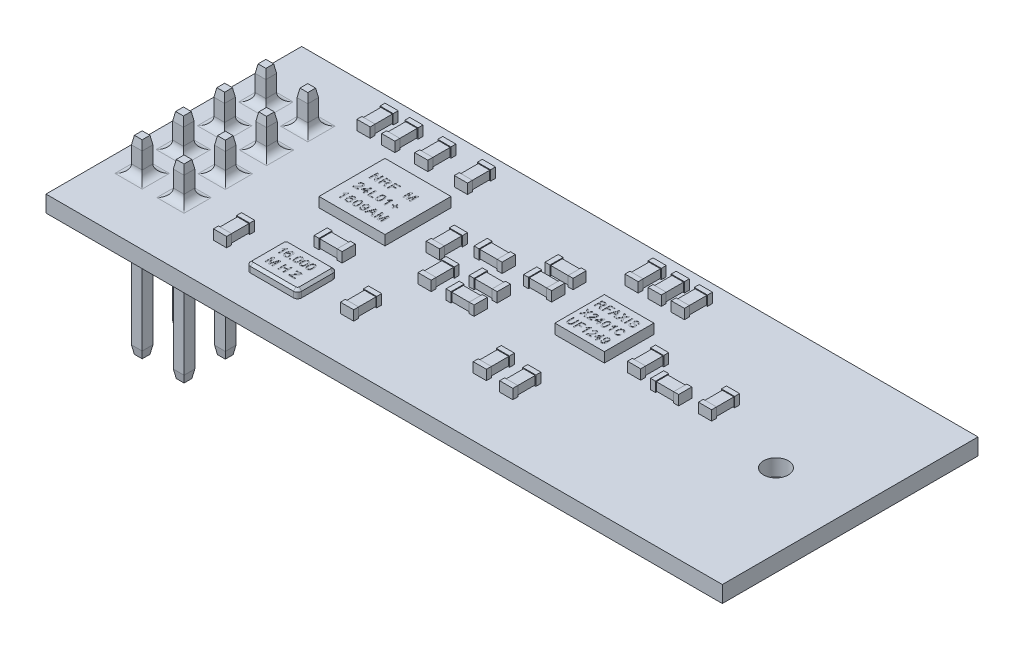
SolidWorks part; units mm, degrees
ref_plane "Спереди" through (0, 0, 0) normal (0, 0, 1) x (1, 0, 0)
ref_plane "Сверху" through (0, 0, 0) normal (0, 1, 0) x (1, 0, 0)
ref_plane "Справа" through (0, 0, 0) normal (1, 0, 0) x (0, 0, -1)
sketch "Эскиз1" plane through (0, 0, 0) normal (0, 1, 0) x (1, 0, 0)
  line L1 (0, -7.75) -> (41, -7.75)
  line L2 (0, -7.75) -> (0, 7.75)
  line L3 (0, 7.75) -> (41, 7.75)
  line L4 (41, -7.75) -> (41, 7.75)
  dimension "D1" = 41
  dimension "D2" = 15.5
extrude "Бобышка-Вытянуть1" add sketch "Эскиз1" along normal blind 1
sketch "Эскиз2" plane through (0, 0, 0) normal (0, -1, 0) x (1, 0, 0)
  line L0 (0, 0) -> (0.6, 0) construction
  line L1 (0, -7.75) -> (0, 7.75) construction
  line L2 (0.6, 4.5) -> (0.6, 3)
  line L3 (0.6, 3) -> (1.1, 2.5)
  line L4 (1.1, 2.5) -> (0.6, 2)
  line L5 (0.6, 2) -> (0.6, 0.5)
  line L6 (0.6, 0.5) -> (1.1, 0)
  line L7 (1.1, 0) -> (0.6, -0.5)
  line L8 (0.6, -0.5) -> (0.6, -2)
  line L9 (0.6, -2) -> (1.1, -2.5)
  line L10 (1.1, -2.5) -> (0.6, -3)
  line L11 (0.6, -3) -> (0.6, -4.5)
  line L12 (0.6, -4.5) -> (1.1, -5)
  line L13 (1.1, -5) -> (5.1, -5)
  line L14 (5.1, -5) -> (5.6, -4.5)
  line L15 (5.6, -4.5) -> (5.6, -3)
  line L16 (5.6, -3) -> (5.1, -2.5)
  line L17 (5.1, -2.5) -> (5.6, -2)
  line L18 (5.6, -2) -> (5.6, -0.5)
  line L19 (5.6, -0.5) -> (5.1, 0)
  line L20 (5.1, 0) -> (5.6, 0.5)
  line L21 (5.6, 0.5) -> (5.6, 2)
  line L22 (5.6, 2) -> (5.1, 2.5)
  line L23 (5.1, 2.5) -> (5.6, 3)
  line L24 (5.6, 3) -> (5.6, 4.5)
  line L25 (5.6, 4.5) -> (5.1, 5)
  line L26 (5.1, 5) -> (1.1, 5)
  line L27 (1.1, 5) -> (0.6, 4.5)
  line L28 (0.6, 0.5) -> (0.6, -0.5) construction
  line L29 (1.1, 2.5) -> (5.1, 2.5) construction
  line L30 (1.1, 0) -> (5.1, 0) construction
  line L31 (1.1, -2.5) -> (5.1, -2.5) construction
  dimension "D1" = 5
  dimension "D2" = 10
  dimension "D3" = 0.5
  dimension "D4" = 0.6
extrude "Бобышка-Вытянуть2" add sketch "Эскиз2" along normal blind 2.5
sketch "Эскиз3" plane through (0, -2.5, 0) normal (0, -1, 0) x (1, 0, 0)
  line L0 (3.1, 5) -> (3.1, -5) construction
  line L1 (5.1, 5) -> (1.1, 5) construction
  line L2 (1.1, -5) -> (5.1, -5) construction
  line L3 (1.83, 3.75) -> (4.37, 3.75) construction
  line L4 (0.6, 3.75) -> (1.83, 3.75) construction
  line L5 (0.6, 4.5) -> (0.6, 3) construction
  line L6 (0.6, 1.25) -> (1.83, 1.25) construction
  line L7 (0.6, 2) -> (0.6, 0.5) construction
  line L8 (1.83, 1.25) -> (4.37, 1.25) construction
  line L9 (4.37, 1.25) -> (4.37, 3.75) construction
  line L10 (1.83, 3.75) -> (1.83, 1.25) construction
  line L11 (0.6, -1.25) -> (1.83, -1.25) construction
  line L12 (0.6, -0.5) -> (0.6, -2) construction
  line L13 (1.83, -1.25) -> (1.83, 1.25) construction
  line L14 (1.83, -1.25) -> (4.37, -1.25) construction
  line L15 (4.37, -1.25) -> (4.37, 1.25) construction
  line L16 (0.6, -3.75) -> (1.83, -3.75) construction
  line L17 (0.6, -3) -> (0.6, -4.5) construction
  line L18 (1.83, -3.75) -> (1.83, -1.25) construction
  line L19 (1.83, -3.75) -> (4.37, -3.75) construction
  line L20 (4.37, -3.75) -> (4.37, -1.25) construction
  line L21 (1.505, 4.075) -> (2.155, 3.425) construction
  line L22 (1.505, 3.425) -> (2.155, 3.425)
  line L23 (1.505, 3.425) -> (1.505, 4.075)
  line L24 (1.505, 4.075) -> (2.155, 4.075)
  line L25 (2.155, 3.425) -> (2.155, 4.075)
  line L26 (4.045, 3.425) -> (4.695, 3.425)
  line L27 (4.045, 3.425) -> (4.045, 4.075)
  line L28 (4.045, 4.075) -> (4.695, 4.075)
  line L29 (4.695, 3.425) -> (4.695, 4.075)
  line L30 (1.505, 0.925) -> (2.155, 0.925)
  line L31 (1.505, 0.925) -> (1.505, 1.575)
  line L32 (1.505, 1.575) -> (2.155, 1.575)
  line L33 (2.155, 0.925) -> (2.155, 1.575)
  line L34 (4.045, 0.925) -> (4.695, 0.925)
  line L35 (4.045, 0.925) -> (4.045, 1.575)
  line L36 (4.045, 1.575) -> (4.695, 1.575)
  line L37 (4.695, 0.925) -> (4.695, 1.575)
  line L38 (1.505, -1.575) -> (2.155, -1.575)
  line L39 (1.505, -1.575) -> (1.505, -0.925)
  line L40 (1.505, -0.925) -> (2.155, -0.925)
  line L41 (2.155, -1.575) -> (2.155, -0.925)
  line L42 (4.045, -1.575) -> (4.695, -1.575)
  line L43 (4.045, -1.575) -> (4.045, -0.925)
  line L44 (4.045, -0.925) -> (4.695, -0.925)
  line L45 (4.695, -1.575) -> (4.695, -0.925)
  line L46 (1.505, -4.075) -> (2.155, -4.075)
  line L47 (1.505, -4.075) -> (1.505, -3.425)
  line L48 (1.505, -3.425) -> (2.155, -3.425)
  line L49 (2.155, -4.075) -> (2.155, -3.425)
  line L50 (4.045, -4.075) -> (4.695, -4.075)
  line L51 (4.045, -4.075) -> (4.045, -3.425)
  line L52 (4.045, -3.425) -> (4.695, -3.425)
  line L53 (4.695, -4.075) -> (4.695, -3.425)
  line L54 (4.045, 4.075) -> (4.695, 3.425) construction
  line L55 (1.505, 1.575) -> (2.155, 0.925) construction
  line L56 (4.045, 1.575) -> (4.695, 0.925) construction
  line L57 (1.505, -0.925) -> (2.155, -1.575) construction
  line L58 (4.045, -0.925) -> (4.695, -1.575) construction
  line L59 (1.505, -3.425) -> (2.155, -4.075) construction
  line L60 (4.045, -3.425) -> (4.695, -4.075) construction
  point P8 (3.1, 3.75)
  dimension "D1" = 2.54
  dimension "D2" = 0.65
extrude "Бобышка-Вытянуть3" add sketch "Эскиз3" along normal blind 6
sketch "Эскиз8" plane through (0, 1, 0) normal (0, 1, 0) x (1, 0, 0)
  line L0 (2.155, -3.425) -> (2.155, -4.075) construction
  line L1 (1.505, 3.425) -> (2.155, 3.425)
  line L2 (1.505, 3.425) -> (1.505, 4.075)
  line L3 (1.505, 4.075) -> (2.155, 4.075)
  line L4 (2.155, 3.425) -> (2.155, 4.075)
  line L5 (4.045, 3.425) -> (4.695, 3.425)
  line L6 (4.045, 3.425) -> (4.045, 4.075)
  line L7 (4.045, 4.075) -> (4.695, 4.075)
  line L8 (4.695, 3.425) -> (4.695, 4.075)
  line L9 (1.505, 0.925) -> (2.155, 0.925)
  line L10 (1.505, 0.925) -> (1.505, 1.575)
  line L11 (1.505, 1.575) -> (2.155, 1.575)
  line L12 (2.155, 0.925) -> (2.155, 1.575)
  line L13 (4.045, 0.925) -> (4.695, 0.925)
  line L14 (4.045, 0.925) -> (4.045, 1.575)
  line L15 (4.045, 1.575) -> (4.695, 1.575)
  line L16 (4.695, 0.925) -> (4.695, 1.575)
  line L17 (1.505, -1.575) -> (2.155, -1.575)
  line L18 (1.505, -1.575) -> (1.505, -0.925)
  line L19 (1.505, -0.925) -> (2.155, -0.925)
  line L20 (2.155, -1.575) -> (2.155, -0.925)
  line L21 (4.045, -1.575) -> (4.695, -1.575)
  line L22 (4.045, -1.575) -> (4.045, -0.925)
  line L23 (4.045, -0.925) -> (4.695, -0.925)
  line L24 (4.695, -1.575) -> (4.695, -0.925)
  line L25 (1.505, -4.075) -> (2.155, -4.075)
  line L26 (1.505, -4.075) -> (1.505, -3.425)
  line L27 (1.505, -3.425) -> (2.155, -3.425)
  line L28 (2.155, -4.075) -> (2.155, -3.425)
  line L30 (4.045, -4.075) -> (4.695, -4.075)
  line L31 (4.045, -4.075) -> (4.045, -3.425)
  line L32 (4.045, -3.425) -> (4.695, -3.425)
  line L33 (4.695, -4.075) -> (4.695, -3.425)
extrude "Бобышка-Вытянуть5" add sketch "Эскиз8" along normal blind 2
chamfer "Фаска1" distance 0.5 angle 10 64 edges at (4.37, -8.5, -4.075) (4.695, -8.5, -3.75) (4.37, -8.5, -3.425) (4.045, -8.5, -3.75) (2.155, -8.5, -3.75) (1.83, -8.5, -4.075) (1.505, -8.5, -3.75) (1.83, -8.5, -3.425) (4.37, -8.5, -1.575) (4.695, -8.5, -1.25) (4.37, -8.5, -0.925) (4.045, -8.5, -1.25) (2.155, -8.5, -1.25) (1.83, -8.5, -1.575) (1.505, -8.5, -1.25) (1.83, -8.5, -0.925) (4.37, -8.5, 0.925) (4.695, -8.5, 1.25) (4.37, -8.5, 1.575) (4.045, -8.5, 1.25) (2.155, -8.5, 1.25) (1.83, -8.5, 0.925) (1.505, -8.5, 1.25) (1.83, -8.5, 1.575) (4.37, -8.5, 3.425) (4.695, -8.5, 3.75) (4.37, -8.5, 4.075) (4.045, -8.5, 3.75) (2.155, -8.5, 3.75) (1.83, -8.5, 4.075) (1.505, -8.5, 3.75) (1.83, -8.5, 3.425) (4.695, 3, -3.75) (4.37, 3, -4.075) (4.045, 3, -3.75) (4.37, 3, -3.425) (2.155, 3, -3.75) (1.83, 3, -4.075) (1.505, 3, -3.75) (1.83, 3, -3.425) (4.695, 3, -1.25) (4.37, 3, -1.575) (4.045, 3, -1.25) (4.37, 3, -0.925) (2.155, 3, -1.25) (1.83, 3, -1.575) (1.505, 3, -1.25) (1.83, 3, -0.925) (4.695, 3, 1.25) (4.37, 3, 0.925) (4.045, 3, 1.25) (4.37, 3, 1.575) (2.155, 3, 1.25) (1.83, 3, 0.925) (1.505, 3, 1.25) (1.83, 3, 1.575) (4.695, 3, 3.75) (4.37, 3, 3.425) (4.045, 3, 3.75) (4.37, 3, 4.075) (2.155, 3, 3.75) (1.83, 3, 3.425) (1.505, 3, 3.75) (1.83, 3, 4.075)
fillet "Скругление1" radius 0.5 32 edges at (1.83, 1, 3.425) (1.505, 1, 3.75) (2.155, 1, 3.75) (1.83, 1, 4.075) (4.695, 1, -3.75) (4.37, 1, -4.075) (4.045, 1, -3.75) (4.37, 1, -3.425) (2.155, 1, -3.75) (1.83, 1, -4.075) (1.505, 1, -3.75) (1.83, 1, -3.425) (4.695, 1, -1.25) (4.37, 1, -1.575) (4.045, 1, -1.25) (4.37, 1, -0.925) (2.155, 1, -1.25) (1.83, 1, -1.575) (1.505, 1, -1.25) (1.83, 1, -0.925) (2.155, 1, 1.25) (1.83, 1, 0.925) (1.505, 1, 1.25) (1.83, 1, 1.575) (4.695, 1, 1.25) (4.37, 1, 0.925) (4.045, 1, 1.25) (4.37, 1, 1.575) (4.695, 1, 3.75) (4.37, 1, 3.425) (4.045, 1, 3.75) (4.37, 1, 4.075)
sketch "Эскиз5" plane through (0, 1, 0) normal (0, 1, 0) x (1, 0, 0)
  line L0 (305.5, -0.012) -> (1527.5, -0.012) construction
  line L1 (41, 0) -> (39.5, 0) construction
  line L2 (33.5, -3) -> (39.5, -3) construction
  line L3 (33.5, -3) -> (33.5, 3) construction
  line L4 (33.5, 3) -> (39.5, 3) construction
  line L5 (39.5, -3) -> (39.5, 3) construction
  line L6 (41, -7.75) -> (41, 7.75) construction
  line L7 (33.5, 3) -> (39.5, -3) construction
  circle A0 centre (36.5, 0) radius 0.75
  dimension "D4" = 1.5
  dimension "D1" = 6
  dimension "D2" = 1.5
  dimension "D3" = 6
sketch "Эскиз9" plane through (0, 1, 0) normal (0, 1, 0) x (1, 0, 0)
  line L0 (6.5, 6.4) -> (6.5, 5.3) construction
  line L1 (6.1, 6.4) -> (6.9, 6.4)
  line L2 (6.1, 6.4) -> (6.1, 6.7)
  line L3 (6.1, 6.7) -> (6.9, 6.7)
  line L4 (6.9, 6.4) -> (6.9, 6.7)
  line L5 (7.6, 6.4) -> (8.4, 6.4)
  line L6 (7.6, 6.4) -> (7.6, 6.7)
  line L7 (7.6, 6.7) -> (8.4, 6.7)
  line L8 (8.4, 6.4) -> (8.4, 6.7)
  line L9 (9.6, 6.4) -> (10.4, 6.4)
  line L10 (9.6, 6.4) -> (9.6, 6.7)
  line L11 (9.6, 6.7) -> (10.4, 6.7)
  line L12 (10.4, 6.4) -> (10.4, 6.7)
  line L13 (12, 6.4) -> (12.8, 6.4)
  line L14 (12, 6.4) -> (12, 6.7)
  line L15 (12, 6.7) -> (12.8, 6.7)
  line L16 (12.8, 6.4) -> (12.8, 6.7)
  line L17 (8, 6.4) -> (8, 5.3) construction
  line L18 (10, 6.4) -> (10, 5.3) construction
  line L19 (12.4, 6.4) -> (12.4, 5.3) construction
  line L20 (7.9, -3.7) -> (7.9, -4.8) construction
  line L21 (6.1, 5) -> (6.9, 5)
  line L22 (6.1, 5) -> (6.1, 5.3)
  line L23 (6.1, 5.3) -> (6.9, 5.3)
  line L24 (6.9, 5) -> (6.9, 5.3)
  line L25 (7.6, 5) -> (8.4, 5)
  line L26 (7.6, 5) -> (7.6, 5.3)
  line L27 (7.6, 5.3) -> (8.4, 5.3)
  line L28 (8.4, 5) -> (8.4, 5.3)
  line L29 (9.6, 5) -> (10.4, 5)
  line L30 (9.6, 5) -> (9.6, 5.3)
  line L31 (9.6, 5.3) -> (10.4, 5.3)
  line L32 (10.4, 5) -> (10.4, 5.3)
  line L33 (12, 5) -> (12.8, 5)
  line L34 (12, 5) -> (12, 5.3)
  line L35 (12, 5.3) -> (12.8, 5.3)
  line L36 (12.8, 5) -> (12.8, 5.3)
  line L37 (7.5, -3.7) -> (8.3, -3.7)
  line L38 (7.5, -3.7) -> (7.5, -3.4)
  line L39 (7.5, -3.4) -> (8.3, -3.4)
  line L40 (8.3, -3.7) -> (8.3, -3.4)
  line L41 (7.5, -5.1) -> (8.3, -5.1)
  line L42 (7.5, -5.1) -> (7.5, -4.8)
  line L43 (7.5, -4.8) -> (8.3, -4.8)
  line L44 (8.3, -5.1) -> (8.3, -4.8)
  line L45 (22.75, 6.4) -> (22.75, 5.3) construction
  line L46 (22.35, 6.7) -> (23.15, 6.7)
  line L47 (22.35, 6.7) -> (22.35, 6.4)
  line L48 (22.35, 6.4) -> (23.15, 6.4)
  line L49 (23.15, 6.7) -> (23.15, 6.4)
  line L50 (23.75, 6.7) -> (24.55, 6.7)
  line L51 (23.75, 6.7) -> (23.75, 6.4)
  line L52 (23.75, 6.4) -> (24.55, 6.4)
  line L53 (24.55, 6.7) -> (24.55, 6.4)
  line L54 (25.15, 6.7) -> (25.95, 6.7)
  line L55 (25.15, 6.7) -> (25.15, 6.4)
  line L56 (25.15, 6.4) -> (25.95, 6.4)
  line L57 (25.95, 6.7) -> (25.95, 6.4)
  line L58 (22.35, 5) -> (23.15, 5)
  line L59 (22.35, 5) -> (22.35, 5.3)
  line L60 (22.35, 5.3) -> (23.15, 5.3)
  line L61 (23.15, 5) -> (23.15, 5.3)
  line L62 (23.75, 5) -> (24.55, 5)
  line L63 (23.75, 5) -> (23.75, 5.3)
  line L64 (23.75, 5.3) -> (24.55, 5.3)
  line L65 (24.55, 5) -> (24.55, 5.3)
  line L66 (25.15, 5) -> (25.95, 5)
  line L67 (25.15, 5) -> (25.15, 5.3)
  line L68 (25.15, 5.3) -> (25.95, 5.3)
  line L69 (25.95, 5) -> (25.95, 5.3)
  line L70 (24.15, 6.4) -> (24.15, 5.3) construction
  line L71 (25.55, 6.4) -> (25.55, 5.3) construction
  line L72 (11.2, -2) -> (12.3, -2) construction
  line L73 (10.9, -2.4) -> (11.2, -2.4)
  line L74 (10.9, -2.4) -> (10.9, -1.6)
  line L75 (10.9, -1.6) -> (11.2, -1.6)
  line L76 (11.2, -2.4) -> (11.2, -1.6)
  line L77 (12.3, -2.4) -> (12.6, -2.4)
  line L78 (12.3, -2.4) -> (12.3, -1.6)
  line L79 (12.3, -1.6) -> (12.6, -1.6)
  line L80 (12.6, -2.4) -> (12.6, -1.6)
  line L81 (15.6, -3.7) -> (15.6, -4.8) construction
  line L82 (15.2, -3.4) -> (16, -3.4)
  line L83 (15.2, -3.4) -> (15.2, -3.7)
  line L84 (15.2, -3.7) -> (16, -3.7)
  line L85 (16, -3.4) -> (16, -3.7)
  line L86 (15.2, -5.1) -> (16, -5.1)
  line L87 (15.2, -5.1) -> (15.2, -4.8)
  line L88 (15.2, -4.8) -> (16, -4.8)
  line L89 (16, -5.1) -> (16, -4.8)
  line L90 (27.4, 1.9) -> (27.4, 0.8) construction
  line L91 (27, 1.9) -> (27.8, 1.9)
  line L92 (27, 1.9) -> (27, 2.2)
  line L93 (27, 2.2) -> (27.8, 2.2)
  line L94 (27.8, 1.9) -> (27.8, 2.2)
  line L95 (27, 0.5) -> (27.8, 0.5)
  line L96 (27, 0.5) -> (27, 0.8)
  line L97 (27, 0.8) -> (27.8, 0.8)
  line L98 (27.8, 0.5) -> (27.8, 0.8)
  line L99 (31.7, 1.9) -> (31.7, 0.8) construction
  line L100 (31.3, 2.2) -> (32.1, 2.2)
  line L101 (31.3, 2.2) -> (31.3, 1.9)
  line L102 (31.3, 1.9) -> (32.1, 1.9)
  line L103 (32.1, 2.2) -> (32.1, 1.9)
  line L104 (31.3, 0.5) -> (32.1, 0.5)
  line L105 (31.3, 0.5) -> (31.3, 0.8)
  line L106 (31.3, 0.8) -> (32.1, 0.8)
  line L107 (32.1, 0.5) -> (32.1, 0.8)
  line L108 (28.9, 0.7) -> (30, 0.7) construction
  line L109 (28.6, 0.3) -> (28.9, 0.3)
  line L110 (28.6, 0.3) -> (28.6, 1.1)
  line L111 (28.6, 1.1) -> (28.9, 1.1)
  line L112 (28.9, 0.3) -> (28.9, 1.1)
  line L113 (30, 0.3) -> (30.3, 0.3)
  line L114 (30, 0.3) -> (30, 1.1)
  line L115 (30, 1.1) -> (30.3, 1.1)
  line L116 (30.3, 0.3) -> (30.3, 1.1)
  line L117 (22.75, -2.8) -> (22.75, -3.9) construction
  line L118 (22.35, -2.8) -> (23.15, -2.8)
  line L119 (22.35, -2.8) -> (22.35, -2.5)
  line L120 (22.35, -2.5) -> (23.15, -2.5)
  line L121 (23.15, -2.8) -> (23.15, -2.5)
  line L122 (22.35, -4.2) -> (23.15, -4.2)
  line L123 (22.35, -4.2) -> (22.35, -3.9)
  line L124 (22.35, -3.9) -> (23.15, -3.9)
  line L125 (23.15, -4.2) -> (23.15, -3.9)
  line L126 (24.55, -3) -> (24.55, -4.1) construction
  line L127 (24.15, -3) -> (24.95, -3)
  line L128 (24.15, -3) -> (24.15, -2.7)
  line L129 (24.15, -2.7) -> (24.95, -2.7)
  line L130 (24.95, -3) -> (24.95, -2.7)
  line L131 (24.15, -4.4) -> (24.95, -4.4)
  line L132 (24.15, -4.4) -> (24.15, -4.1)
  line L133 (24.15, -4.1) -> (24.95, -4.1)
  line L134 (24.95, -4.4) -> (24.95, -4.1)
  line L135 (16.4, 0.2) -> (16.4, -0.9) construction
  line L136 (16, -1.2) -> (16.8, -1.2)
  line L137 (16, -1.2) -> (16, -0.9)
  line L138 (16, -0.9) -> (16.8, -0.9)
  line L139 (16.8, -1.2) -> (16.8, -0.9)
  line L140 (16, 0.2) -> (16.8, 0.2)
  line L141 (16, 0.2) -> (16, 0.5)
  line L142 (16, 0.5) -> (16.8, 0.5)
  line L143 (16.8, 0.2) -> (16.8, 0.5)
  line L144 (15, 2.1) -> (15, 1) construction
  line L145 (14.6, 0.7) -> (15.4, 0.7)
  line L146 (14.6, 0.7) -> (14.6, 1)
  line L147 (14.6, 1) -> (15.4, 1)
  line L148 (15.4, 0.7) -> (15.4, 1)
  line L149 (14.6, 2.1) -> (15.4, 2.1)
  line L150 (14.6, 2.1) -> (14.6, 2.4)
  line L151 (14.6, 2.4) -> (15.4, 2.4)
  line L152 (15.4, 2.1) -> (15.4, 2.4)
  line L153 (16.6, 2.3) -> (17.7, 2.3) construction
  line L154 (16.3, 1.9) -> (16.6, 1.9)
  line L155 (16.3, 1.9) -> (16.3, 2.7)
  line L156 (16.3, 2.7) -> (16.6, 2.7)
  line L157 (16.6, 1.9) -> (16.6, 2.7)
  line L158 (17.7, 1.9) -> (18, 1.9)
  line L159 (17.7, 1.9) -> (17.7, 2.7)
  line L160 (17.7, 2.7) -> (18, 2.7)
  line L161 (18, 1.9) -> (18, 2.7)
  line L162 (19.3, 1.9) -> (19.6, 1.9)
  line L163 (19.3, 1.9) -> (19.3, 2.7)
  line L164 (19.3, 2.7) -> (19.6, 2.7)
  line L165 (19.6, 1.9) -> (19.6, 2.7)
  line L166 (20.7, 1.9) -> (21, 1.9)
  line L167 (20.7, 1.9) -> (20.7, 2.7)
  line L168 (20.7, 2.7) -> (21, 2.7)
  line L169 (21, 1.9) -> (21, 2.7)
  line L170 (19.3, 3.2) -> (19.6, 3.2)
  line L171 (19.3, 3.2) -> (19.3, 4)
  line L172 (19.3, 4) -> (19.6, 4)
  line L173 (19.6, 3.2) -> (19.6, 4)
  line L174 (20.7, 3.2) -> (21, 3.2)
  line L175 (20.7, 3.2) -> (20.7, 4)
  line L176 (20.7, 4) -> (21, 4)
  line L177 (21, 3.2) -> (21, 4)
  line L178 (19.6, 2.3) -> (20.7, 2.3) construction
  line L179 (19.6, 3.6) -> (20.7, 3.6) construction
  line L180 (18, 0.6) -> (19.1, 0.6) construction
  line L181 (17.7, -1.2) -> (18, -1.2)
  line L182 (17.7, -1.2) -> (17.7, -0.4)
  line L183 (17.7, -0.4) -> (18, -0.4)
  line L184 (18, -1.2) -> (18, -0.4)
  line L185 (19.1, -1.2) -> (19.4, -1.2)
  line L186 (19.1, -1.2) -> (19.1, -0.4)
  line L187 (19.1, -0.4) -> (19.4, -0.4)
  line L188 (19.4, -1.2) -> (19.4, -0.4)
  line L189 (17.7, 0.2) -> (18, 0.2)
  line L190 (17.7, 0.2) -> (17.7, 1)
  line L191 (17.7, 1) -> (18, 1)
  line L192 (18, 0.2) -> (18, 1)
  line L193 (19.1, 0.2) -> (19.4, 0.2)
  line L194 (19.1, 0.2) -> (19.1, 1)
  line L195 (19.1, 1) -> (19.4, 1)
  line L196 (19.4, 0.2) -> (19.4, 1)
  line L197 (18, -0.8) -> (19.1, -0.8) construction
  dimension "D1" = 1.7
  dimension "D2" = 0.8
  dimension "D3" = 6.5
  dimension "D4" = 5
  dimension "D5" = 0.3
  dimension "D6" = 1.5
  dimension "D7" = 2
  dimension "D8" = 2.4
  dimension "D9" = 0.8
  dimension "D10" = 1.7
  dimension "D11" = 0.3
  dimension "D12" = 3.4
  dimension "D13" = 7.9
  dimension "D14" = 10.35
  dimension "D15" = 1.4
  dimension "D16" = 1.4
  dimension "D17" = 1.7
  dimension "D18" = 0.8
  dimension "D19" = 0.3
  dimension "D20" = 2
  dimension "D21" = 10.9
  dimension "D22" = 7.7
  dimension "D23" = 1.7
  dimension "D24" = 0.8
  dimension "D25" = 0.3
  dimension "D26" = 27.4
  dimension "D27" = 0.5
  dimension "D28" = 4.3
  dimension "D29" = 1.7
  dimension "D30" = 1.2
  dimension "D31" = 0.3
  dimension "D32" = 1.5
  dimension "D33" = 1.7
  dimension "D34" = 0.8
  dimension "D35" = 0.3
  dimension "D36" = 7.15
  dimension "D37" = 2.5
  dimension "D38" = 1.8
  dimension "D39" = 0.2
  dimension "D40" = 0.8
  dimension "D41" = 1.7
  dimension "D42" = 0.3
  dimension "D43" = 1.2
  dimension "D44" = 16.4
  dimension "D45" = 1.4
  dimension "D46" = 0.2
  dimension "D47" = 1.8
  dimension "D48" = 1.3
  dimension "D49" = 1.3
  dimension "D50" = 1.3
  dimension "D51" = 1.3
  dimension "D52" = 1.4
  dimension "D53" = 0.4
extrude "Бобышка-Вытянуть6" add sketch "Эскиз9" along normal blind 0.6
sketch "Эскиз10" plane through (0, 1, 0) normal (0, 1, 0) x (1, 0, 0)
  line L0 (6.1, 6.4) -> (6.9, 6.4) construction
  line L1 (7.6, 6.4) -> (8.4, 6.4) construction
  line L2 (9.6, 6.4) -> (10.4, 6.4) construction
  line L3 (12, 6.4) -> (12.8, 6.4) construction
  line L4 (6.9, 5.3) -> (6.1, 5.3) construction
  line L5 (6.15, 5.3) -> (6.85, 5.3)
  line L6 (6.15, 5.3) -> (6.15, 6.4)
  line L7 (6.15, 6.4) -> (6.85, 6.4)
  line L8 (6.85, 5.3) -> (6.85, 6.4)
  line L9 (8.4, 5.3) -> (7.6, 5.3) construction
  line L10 (7.65, 5.3) -> (8.35, 5.3)
  line L11 (7.65, 5.3) -> (7.65, 6.4)
  line L12 (7.65, 6.4) -> (8.35, 6.4)
  line L13 (8.35, 5.3) -> (8.35, 6.4)
  line L14 (10.4, 5.3) -> (9.6, 5.3) construction
  line L15 (9.65, 5.3) -> (10.35, 5.3)
  line L16 (9.65, 5.3) -> (9.65, 6.4)
  line L17 (9.65, 6.4) -> (10.35, 6.4)
  line L18 (10.35, 5.3) -> (10.35, 6.4)
  line L19 (12.8, 5.3) -> (12, 5.3) construction
  line L20 (12.05, 5.3) -> (12.75, 5.3)
  line L21 (12.05, 5.3) -> (12.05, 6.4)
  line L22 (12.05, 6.4) -> (12.75, 6.4)
  line L23 (12.75, 5.3) -> (12.75, 6.4)
  line L24 (7.5, -3.7) -> (8.3, -3.7) construction
  line L25 (22.35, 6.4) -> (23.15, 6.4) construction
  line L26 (23.75, 6.4) -> (24.55, 6.4) construction
  line L27 (25.15, 6.4) -> (25.95, 6.4) construction
  line L28 (8.3, -4.8) -> (7.5, -4.8) construction
  line L29 (7.55, -4.8) -> (8.25, -4.8)
  line L30 (7.55, -4.8) -> (7.55, -3.7)
  line L31 (7.55, -3.7) -> (8.25, -3.7)
  line L32 (8.25, -4.8) -> (8.25, -3.7)
  line L33 (23.15, 5.3) -> (22.35, 5.3) construction
  line L34 (22.4, 5.3) -> (23.1, 5.3)
  line L35 (22.4, 5.3) -> (22.4, 6.4)
  line L36 (22.4, 6.4) -> (23.1, 6.4)
  line L37 (23.1, 5.3) -> (23.1, 6.4)
  line L38 (24.55, 5.3) -> (23.75, 5.3) construction
  line L39 (23.8, 5.3) -> (24.5, 5.3)
  line L40 (23.8, 5.3) -> (23.8, 6.4)
  line L41 (23.8, 6.4) -> (24.5, 6.4)
  line L42 (24.5, 5.3) -> (24.5, 6.4)
  line L43 (23.75, 6.4) -> (24.55, 6.4) construction
  line L44 (25.95, 5.3) -> (25.15, 5.3) construction
  line L45 (25.2, 5.3) -> (25.9, 5.3)
  line L46 (25.2, 5.3) -> (25.2, 6.4)
  line L47 (25.2, 6.4) -> (25.9, 6.4)
  line L48 (25.9, 5.3) -> (25.9, 6.4)
  line L49 (25.15, 6.4) -> (25.95, 6.4) construction
  line L50 (11.2, -2.4) -> (11.2, -1.6) construction
  line L51 (12.3, -1.6) -> (12.3, -2.4) construction
  line L52 (11.2, -2.35) -> (12.3, -2.35)
  line L53 (11.2, -2.35) -> (11.2, -1.65)
  line L54 (11.2, -1.65) -> (12.3, -1.65)
  line L55 (12.3, -2.35) -> (12.3, -1.65)
  line L56 (15.2, -3.7) -> (16, -3.7) construction
  line L57 (16, -4.8) -> (15.2, -4.8) construction
  line L58 (15.25, -4.8) -> (15.95, -4.8)
  line L59 (15.25, -4.8) -> (15.25, -3.7)
  line L60 (15.25, -3.7) -> (15.95, -3.7)
  line L61 (15.95, -4.8) -> (15.95, -3.7)
  line L62 (15.2, -3.7) -> (16, -3.7) construction
  line L63 (27, 1.9) -> (27.8, 1.9) construction
  line L64 (27.8, 0.8) -> (27, 0.8) construction
  line L65 (27.05, 0.8) -> (27.75, 0.8)
  line L66 (27.05, 0.8) -> (27.05, 1.9)
  line L67 (27.05, 1.9) -> (27.75, 1.9)
  line L68 (27.75, 0.8) -> (27.75, 1.9)
  line L69 (27, 1.9) -> (27.8, 1.9) construction
  line L70 (31.3, 1.9) -> (32.1, 1.9) construction
  line L71 (32.1, 0.8) -> (31.3, 0.8) construction
  line L72 (31.35, 0.8) -> (32.05, 0.8)
  line L73 (31.35, 0.8) -> (31.35, 1.9)
  line L74 (31.35, 1.9) -> (32.05, 1.9)
  line L75 (32.05, 0.8) -> (32.05, 1.9)
  line L76 (28.9, 0.3) -> (28.9, 1.1) construction
  line L77 (28.9, 0.3) -> (28.9, 1.1) construction
  line L78 (28.9, 0.35) -> (30, 0.35)
  line L79 (28.9, 0.35) -> (28.9, 1.05)
  line L80 (28.9, 1.05) -> (30, 1.05)
  line L81 (30, 0.35) -> (30, 1.05)
  line L82 (30, 1.1) -> (30, 0.3) construction
  line L83 (22.35, -2.8) -> (23.15, -2.8) construction
  line L84 (24.15, -3) -> (24.95, -3) construction
  line L85 (23.15, -3.9) -> (22.35, -3.9) construction
  line L86 (22.4, -3.9) -> (23.1, -3.9)
  line L87 (22.4, -3.9) -> (22.4, -2.8)
  line L88 (22.4, -2.8) -> (23.1, -2.8)
  line L89 (23.1, -3.9) -> (23.1, -2.8)
  line L90 (24.95, -4.1) -> (24.15, -4.1) construction
  line L91 (24.2, -4.1) -> (24.9, -4.1)
  line L92 (24.2, -4.1) -> (24.2, -3)
  line L93 (24.2, -3) -> (24.9, -3)
  line L94 (24.9, -4.1) -> (24.9, -3)
  line L95 (16, 0.2) -> (16.8, 0.2) construction
  line L96 (16.8, -0.9) -> (16, -0.9) construction
  line L97 (16.05, -0.9) -> (16.75, -0.9)
  line L98 (16.05, -0.9) -> (16.05, 0.2)
  line L99 (16.05, 0.2) -> (16.75, 0.2)
  line L100 (16.75, -0.9) -> (16.75, 0.2)
  line L101 (14.6, 2.1) -> (15.4, 2.1) construction
  line L102 (15.4, 1) -> (14.6, 1) construction
  line L103 (14.65, 1) -> (15.35, 1)
  line L104 (14.65, 1) -> (14.65, 2.1)
  line L105 (14.65, 2.1) -> (15.35, 2.1)
  line L106 (15.35, 1) -> (15.35, 2.1)
  line L107 (14.6, 2.1) -> (15.4, 2.1) construction
  line L108 (16.6, 1.9) -> (16.6, 2.7) construction
  line L109 (19.6, 3.2) -> (19.6, 4) construction
  line L110 (19.6, 1.9) -> (19.6, 2.7) construction
  line L111 (17.7, 2.7) -> (17.7, 1.9) construction
  line L112 (16.6, 1.95) -> (17.7, 1.95)
  line L113 (16.6, 1.95) -> (16.6, 2.65)
  line L114 (16.6, 2.65) -> (17.7, 2.65)
  line L115 (17.7, 1.95) -> (17.7, 2.65)
  line L116 (20.7, 2.7) -> (20.7, 1.9) construction
  line L117 (19.6, 1.95) -> (20.7, 1.95)
  line L118 (19.6, 1.95) -> (19.6, 2.65)
  line L119 (19.6, 2.65) -> (20.7, 2.65)
  line L120 (20.7, 1.95) -> (20.7, 2.65)
  line L121 (20.7, 4) -> (20.7, 3.2) construction
  line L122 (19.6, 3.25) -> (20.7, 3.25)
  line L123 (19.6, 3.25) -> (19.6, 3.95)
  line L124 (19.6, 3.95) -> (20.7, 3.95)
  line L125 (20.7, 3.25) -> (20.7, 3.95)
  line L126 (18, -1.2) -> (18, -0.4) construction
  line L127 (18, 0.2) -> (18, 1) construction
  line L128 (19.1, -0.4) -> (19.1, -1.2) construction
  line L129 (18, -1.15) -> (19.1, -1.15)
  line L130 (18, -1.15) -> (18, -0.45)
  line L131 (18, -0.45) -> (19.1, -0.45)
  line L132 (19.1, -1.15) -> (19.1, -0.45)
  line L133 (19.1, 1) -> (19.1, 0.2) construction
  line L134 (18, 0.25) -> (19.1, 0.25)
  line L135 (18, 0.25) -> (18, 0.95)
  line L136 (18, 0.95) -> (19.1, 0.95)
  line L137 (19.1, 0.25) -> (19.1, 0.95)
  point P0 (6.5, 6.4)
  point P1 (8, 6.4)
  point P4 (10, 6.4)
  point P7 (12.4, 6.4)
  point P36 (22.75, 6.4)
  point P37 (7.9, -3.7)
  point P38 (24.15, 6.4)
  point P43 (25.55, 6.4)
  point P77 (11.2, -2)
  point P85 (15.6, -3.7)
  point P97 (27.4, 1.9)
  point P107 (31.7, 1.9)
  point P116 (28.9, 0.7)
  point P127 (22.75, -2.8)
  point P128 (24.55, -3)
  point P147 (16.4, 0.2)
  point P155 (15, 2.1)
  point P165 (19.6, 3.6)
  point P166 (16.6, 2.3)
  point P167 (19.6, 2.3)
  point P192 (18, 0.6)
  point P195 (18, -0.8)
  dimension "D1" = 0.7
extrude "Бобышка-Вытянуть7" add sketch "Эскиз10" along normal blind 0.5 from offset 0.05
sketch "Эскиз12" plane through (0, 1, 0) normal (0, 1, 0) x (1, 0, 0)
  line L0 (9, 1.8) -> (13, 1.8) construction
  line L1 (9, -0.2) -> (13, -0.2)
  line L2 (9, -0.2) -> (9, 3.8)
  line L3 (9, 3.8) -> (13, 3.8)
  line L4 (13, -0.2) -> (13, 3.8)
  line L5 (22.8, 1.8) -> (25.8, 1.8) construction
  line L6 (22.8, 0.3) -> (25.8, 0.3)
  line L7 (22.8, 0.3) -> (22.8, 3.3)
  line L8 (22.8, 3.3) -> (25.8, 3.3)
  line L9 (25.8, 0.3) -> (25.8, 3.3)
  dimension "D1" = 4
  dimension "D2" = 4
  dimension "D3" = 9
  dimension "D4" = 0.2
  dimension "D5" = 3
  dimension "D6" = 0.3
  dimension "D7" = 22.8
extrude "Бобышка-Вытянуть9" add sketch "Эскиз12" along normal blind 0.6
sketch "Эскиз13" plane through (0, 1.6, 0) normal (0, 1, 0) x (1, 0, 0)
  line L0 (9, 2.3) -> (12.1601, 2.3) construction
  line L1 (9, 3.8) -> (9, -0.2) construction
  text T0 "  NRF  M\r\n  24L01+\r\n  1609AM" font "Arial" height 0.5
  dimension "D1" = 1.5
extrude "Вырез-Вытянуть2" cut sketch "Эскиз13" against normal blind 0.01
sketch "Эскиз15" plane through (0, 1.6, 0) normal (0, 1, 0) x (1, 0, 0)
  line L0 (22.8, 2.4) -> (25.8, 2.4) construction
  line L1 (22.8, 3.3) -> (22.8, 0.3) construction
  line L2 (25.8, 0.3) -> (25.8, 3.3) construction
  text T0 " RFAXIS\r\n X2401C\r\n UF1249" font "Arial" height 0.5
  dimension "D1" = 0.9
extrude "Вырез-Вытянуть4" cut sketch "Эскиз15" against normal blind 0.01
sketch "Эскиз17" plane through (0, 1, 0) normal (0, 1, 0) x (1, 0, 0)
  line L0 (11.65, -3.3) -> (11.65, -5.7) construction
  line L1 (10.35, -5.7) -> (12.95, -5.7)
  line L2 (10.1, -5.45) -> (10.1, -3.55)
  line L3 (10.35, -3.3) -> (12.95, -3.3)
  line L4 (13.2, -5.45) -> (13.2, -3.55)
  arc A0 (10.35, -5.7) -> (10.1, -5.45) centre (10.35, -5.45) cw
  arc A1 (12.95, -5.7) -> (13.2, -5.45) centre (12.95, -5.45) ccw
  arc A2 (12.95, -3.3) -> (13.2, -3.55) centre (12.95, -3.55) cw
  arc A3 (10.1, -3.55) -> (10.35, -3.3) centre (10.35, -3.55) cw
  dimension "D1" = 0.25
  dimension "D2" = 3.1
  dimension "D3" = 2.4
  dimension "D4" = 10.1
  dimension "D5" = 5.7
extrude "Бобышка-Вытянуть10" add sketch "Эскиз17" along normal blind 0.5
chamfer "Фаска3" distance 0.15 angle 45 8 edges at (11.65, 1.5, 3.3) (10.1732, 1.5, 3.3732) (13.1268, 1.5, 3.3732) (10.1, 1.5, 4.5) (13.2, 1.5, 4.5) (10.1732, 1.5, 5.6268) (13.1268, 1.5, 5.6268) (11.65, 1.5, 5.7)
sketch "Эскиз18" plane through (0, 1.5, 0) normal (0, 1, 0) x (1, 0, 0)
  line L0 (10.25, -4.3) -> (13.05, -4.3) construction
  line L1 (10.25, -3.55) -> (10.25, -5.45) construction
  line L2 (13.05, -5.45) -> (13.05, -3.55) construction
  line L3 (12.95, -3.45) -> (10.35, -3.45) construction
  text T0 " 16.000\r\n  M H Z" font "Arial" height 0.5
  dimension "D1" = 0.85
extrude "Вырез-Вытянуть5" cut sketch "Эскиз18" against normal blind 0.01
extrude "Cut-Extrude1" cut sketch "Эскиз5" against normal blind 10
equation "\"D4@Эскиз6\"=\"D2@Эскиз6\""
equation "\"D5@Эскиз6\"=\"D2@Эскиз6\""
